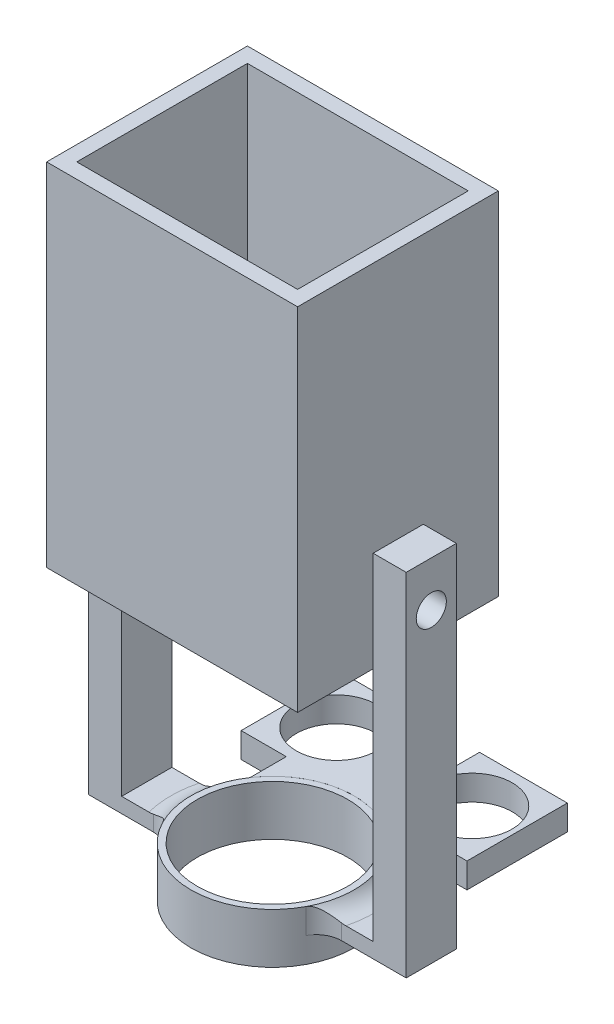
SolidWorks part; units mm, degrees
ref_plane "Front Plane" through (0, 0, 0) normal (0, 0, 1) x (1, 0, 0)
ref_plane "Top Plane" through (0, 0, 0) normal (0, 1, 0) x (1, 0, 0)
ref_plane "Right Plane" through (0, 0, 0) normal (1, 0, 0) x (0, 0, -1)
sketch "Sketch2" plane through (0, 0, 0) normal (0, 1, 0) x (1, 0, 0)
  line L0 (0, 15) -> (0, -15) construction
  line L1 (-15, 0) -> (15, 0) construction
  line L2 (-15, 0) -> (-15, 5) construction
  line L3 (-14.1421, 5) -> (-31.6421, 5)
  line L4 (-31.6421, 5) -> (-31.6421, -5)
  line L5 (-14.1421, -5) -> (-31.6421, -5)
  line L6 (14.1421, -5) -> (31.6421, -5)
  line L7 (31.6421, 5) -> (31.6421, -5)
  line L8 (14.1421, 5) -> (31.6421, 5)
  line L9 (0, 16.25) -> (22.5, 16.25)
  line L10 (22.5, 16.25) -> (22.5, 36.25)
  line L11 (22.5, 36.25) -> (5, 36.25)
  line L12 (-22.5, 36.25) -> (-22.5, 16.25)
  line L13 (-22.5, 16.25) -> (0, 16.25)
  line L14 (22.5, 26.25) -> (21.5, 26.25) construction
  line L20 (-5, 36.25) -> (-22.5, 36.25)
  line L21 (0, 31.25) -> (0, 16.25) construction
  line L22 (-5, 36.25) -> (-5, 31.25)
  line L23 (-5, 31.25) -> (5, 31.25)
  line L24 (5, 31.25) -> (5, 36.25)
  line L25 (13.5, 34.25) -> (13.5, 36.25) construction
  line L26 (13.5, 18.25) -> (13.5, 16.25) construction
  line L27 (-13.5, 26.25) -> (13.5, 26.25) construction
  line L28 (-13.5, 9.045) -> (-13.5, 16.25)
  line L29 (13.5, 16.25) -> (13.5, 9.045)
  line L30 (-16.25, 0) -> (-25.05, 0) construction
  line L31 (-25.05, 5) -> (-25.05, -5)
  line L32 (25.05, 5) -> (25.05, -5)
  circle A0 centre (0, 0) radius 15
  circle A1 centre (0, 0) radius 16.25
  circle A2 centre (13.5, 26.25) radius 8
  circle A3 centre (-13.5, 26.25) radius 8
  point P13 (-31.6421, 0)
  dimension "D1" = 30
  dimension "D2" = 17.5
  dimension "D4" = 32.5
  dimension "D8" = 1
  dimension "D9" = 16
  dimension "D3" = 5
  dimension "D5" = 5
  dimension "D6" = 20
  dimension "D7" = 45
  dimension "D10" = 17.5
  dimension "D11" = 8.8
extrude "Connector sleeve" add sketch "Sketch2" along normal blind 5 and the other way blind 5 contours L5 A1 L6 A0 | L8 A1 L3 A0 | L6 A1 L8 A0 | L3 A1 L5 A0 region at (-14.3253, 0, -6.9471) region at (-15.3497, 0, 0) region at (-14.8019, 0, 5.3291) region at (15.3497, 0, 0)
ref_plane "Plane2" through (0, 30, 0) normal (0, 1, 0) x (1, 0, 0)
sketch "Sketch3" plane through (0, 30, 0) normal (0, 1, 0) x (1, 0, 0)
  line L1 (-25, 20) -> (25, 20)
  line L2 (-25, 20) -> (-25, -20)
  line L3 (-25, -20) -> (25, -20)
  line L4 (25, 20) -> (25, -20)
  line L5 (-25, 20) -> (25, -20) construction
  line L6 (-25, -20) -> (25, 20) construction
  circle A0 centre (0, 0) radius 3
  point P0 (0, 0)
  dimension "D3" = 6
  dimension "D1" = 50
  dimension "D2" = 40
extrude "Motor casing" add sketch "Sketch3" along normal blind 70
shell "Shell4" thickness 3 removed face at (0, 100, 3) removed face at (0, 100, 0)
sketch "Sketch6" plane through (0, 33, 0) normal (0, 1, 0) x (1, 0, 0)
  circle A0 centre (0, 0) radius 15
  circle A1 centre (0, 0) radius 16
  dimension "D1" = 30
  dimension "D2" = 32
extrude "Motor sits here" add sketch "Sketch6" along normal blind 30
extrude "Sleeve-casing connector" add sketch "Sketch2<16>" along normal blind 3 contours A1 L3 L31 L5 | L31 L3 L4 L5 | A1 L6 L32 L8 | L8 L32 L6 L7 region at (-28.3461, 0, 0) region at (-20.5169, 0, 0) region at (20.5169, 0, 0) region at (28.3461, 0, 0)
sketch "Sketch2<16>" plane through (0, 0, 0) normal (0, 1, 0) x (1, 0, 0) same geometry as "Sketch2"
extrude "Sleeve-casing arms" add sketch "Sketch2<17>" along normal blind 70 contours L31 L3 L4 L5 | L8 L32 L6 L7 region at (-28.3461, 0, 0) region at (28.3461, 0, 0)
sketch "Sketch2<17>" plane through (0, 0, 0) normal (0, 1, 0) x (1, 0, 0) same geometry as "Sketch2"
extrude "Sensor holder" add sketch "Sketch2<10>" along normal blind 5 separate body contours L24 L23 L22 L20 L12 L13 L9 L10 L11 A2 A3 | A1 L13 L28 | A1 L29 L9 region at (-10.2927, 0, -14.2057) region at (0, 0, -25.4127) region at (10.2927, 0, -14.2057)
sketch "Sketch2<10>" plane through (0, 0, 0) normal (0, 1, 0) x (1, 0, 0) same geometry as "Sketch2"
fillet "Fillet2" radius 5 6 edges at (-15.4616, 1.5, -5) (-16.25, 3, 0) (-15.4616, 1.5, 5) (15.4616, 1.5, 5) (15.4616, 1.5, -5) (16.25, 3, 0)
ref_plane "Plane4" through (-31.6421, 0, 0) normal (-1, 0, 0) x (0, 0, 1)
sketch "Sketch8" plane through (-31.6421, 0, 0) normal (-1, 0, 0) x (0, 0, 1)
  line L0 (0, 70) -> (0, 61) construction
  line L1 (-5, 70) -> (5, 70) construction
  circle A0 centre (0, 61) radius 3
  dimension "D2" = 3
  dimension "D1" = 9
extrude "Cut-Extrude5" cut sketch "Sketch8" against normal through all both and the other way through all
move or copy body "Body-Move/Copy2" bodies to move or copy 103 104 copy no translate (0, 20, 0) parameters "D1"=0, "D2"=20, "D3"=0
